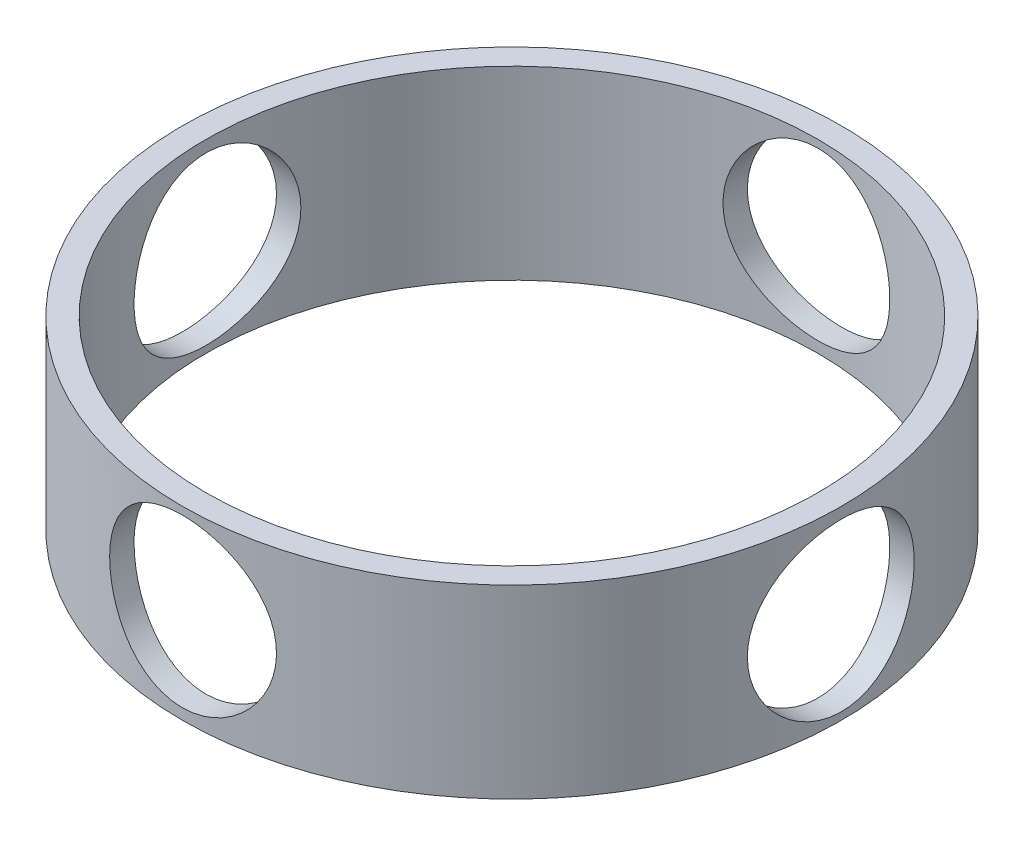
SolidWorks part; units mm, degrees
ref_plane "Front Plane" through (0, 0, 0) normal (0, 0, 1) x (1, 0, 0)
ref_plane "Top Plane" through (0, 0, 0) normal (0, 1, 0) x (1, 0, 0)
ref_plane "Right Plane" through (0, 0, 0) normal (1, 0, 0) x (0, 0, -1)
sketch "Sketch1" plane through (0, 0, 0) normal (0, 1, 0) x (1, 0, 0)
  circle A0 centre (0, 0) radius 88.9
  dimension "D1" = 177.8
extrude "Boss-Extrude1" add sketch "Sketch1" along normal blind 50
sketch "Sketch2" plane through (0, 0, 0) normal (0, 1, 0) x (1, 0, 0)
  circle A0 centre (0, 0) radius 82.55
  dimension "D1" = 165.1
extrude "Cut-Extrude4" cut sketch "Sketch2" along normal blind 74 contours A0
sketch "Sketch12" plane through (0, 0, 0) normal (1, 0, 0) x (0, 0, -1)
  circle A0 centre (0, 24.3361) radius 22.5
  dimension "D1" = 45
extrude "Cut-Extrude5" cut sketch "Sketch12" against normal blind 115.64
sketch "Sketch13" plane through (0, 0, 0) normal (0, 0, 1) x (1, 0, 0)
  circle A0 centre (0, 25.4507) radius 22.5
extrude "Cut-Extrude6" cut sketch "Sketch13" against normal blind 115.64
sketch "Sketch14" plane through (0, 0, 0) normal (1, 0, 0) x (0, 0, -1)
  circle A0 centre (0, 24.5219) radius 22.5
extrude "Cut-Extrude7" cut sketch "Sketch14" along normal blind 99.64
sketch "Sketch15" plane through (0, 0, 0) normal (0, 0, 1) x (1, 0, 0)
  circle A0 centre (0, 25.4507) radius 22.5
extrude "Cut-Extrude8" cut sketch "Sketch15" along normal blind 137.64
ref_axis "Axis1" through (0, 25.4507, 88.9) along (0, 0, 1)
